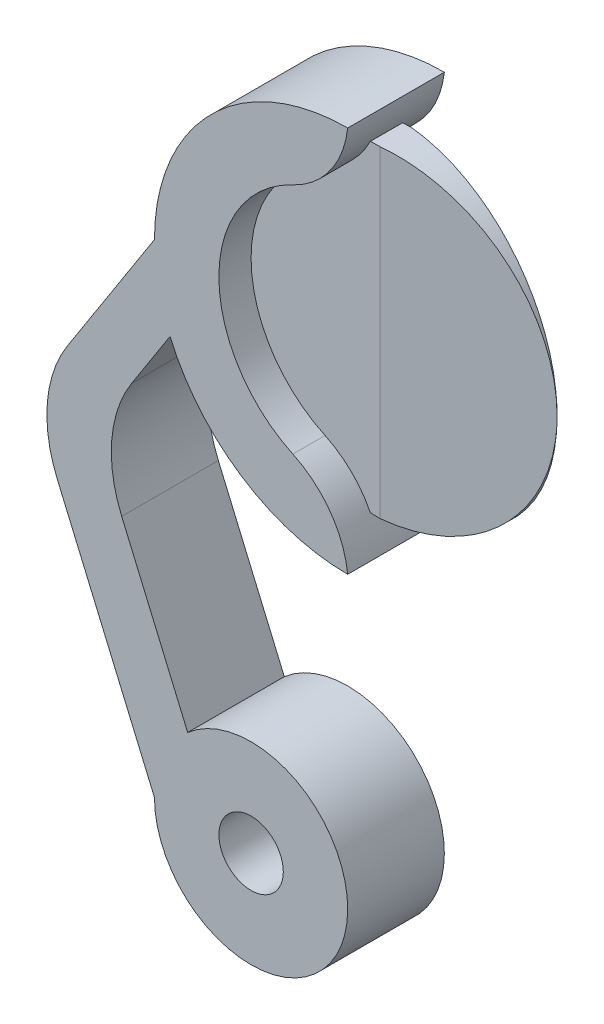
SolidWorks part; units mm, degrees
ref_plane "Front Plane" through (0, 0, 0) normal (0, 0, 1) x (1, 0, 0)
ref_plane "Top Plane" through (0, 0, 0) normal (0, 1, 0) x (1, 0, 0)
ref_plane "Right Plane" through (0, 0, 0) normal (1, 0, 0) x (0, 0, -1)
sketch "Sketch1" plane through (0, 0, 0) normal (0, 0, 1) x (1, 0, 0)
  line L0 (0, 0) -> (0, -120) construction
  line L1 (0, 0) -> (0, -10)
  line L2 (0, -50) -> (0, -60)
  line L4 (-30, -30) -> (-49.2547, -60)
  line L5 (-49.2547, -60) -> (-30, -105)
  line L6 (-20, -30) -> (-39.2547, -60)
  line L7 (-39.2547, -60) -> (-20, -105)
  line L8 (-30, -30) -> (-20, -30)
  line L9 (-30, -105) -> (-20, -105)
  arc A0 (0, -10) -> (0, -50) centre (0, -30) ccw
  arc A1 (0, 0) -> (0, -60) centre (0, -30) ccw
  circle A2 centre (-15, -105) radius 15
  circle A3 centre (-15, -105) radius 5
  dimension "D1" = 40
  dimension "D2" = 60
  dimension "D5" = 15
  dimension "D6" = 15
  dimension "D4" = 120
  dimension "D7" = 10
  dimension "D8" = 15
extrude "Boss-Extrude1" add sketch "Sketch1" along normal blind 15 contours L8 A1 L6 | L1 A1 L8 A0 | L6 A1 L2 A0 | A2 L7 L6 A1 L4 L5 | L7 A2 L9 | L7 A3 L9 A2 region at (-16.1277, -13.8723, 0) region at (-36.5183, -67.2913, 0) region at (-26.1035, -34.0913, 0) region at (-14.1866, -48.4697, 0) region at (-25.4415, -100.8757, 0) region at (-25, -105.4243, 0)
fillet "Fillet1" radius 20 2 edges at (-39.2547, -60, 7.5) (-49.2547, -60, 7.5)
fillet "Fillet2" radius 15 2 edges at (0, -50, 7.5) (0, -10, 7.5)
sketch "Sketch2" plane through (0, 0, 0) normal (1, 0, 0) x (0, 0, -1)
  line L0 (-15, 0) -> (0, 0) construction
  line L1 (-10, 0) -> (-5, 0)
  line L2 (-10, 0) -> (-10, -60)
  line L3 (-10, -60) -> (-5, -60)
  line L4 (-5, 0) -> (-5, -60)
  line L5 (-15, -60) -> (0, -60) construction
  line L6 (0, -48.0952) -> (0, -11.9048) construction
  dimension "D1" = 5
  dimension "D2" = 5
extrude "Boss-Extrude2" add sketch "Sketch2" along normal blind 25 and the other way blind 21
sketch "Sketch3" plane through (0, 0, 5) normal (0, 0, -1) x (-1, 0, 0)
  line L1 (-25, 0) -> (21, 0)
  line L2 (-25, 0) -> (-25, -60)
  line L3 (-25, -60) -> (21, -60)
  line L4 (21, 0) -> (21, -60)
  arc A0 (21, -16.4353) -> (21, -43.5647) centre (0, -30) ccw
  arc A1 (0, -60) -> (21, -51.4243) centre (0, -30) ccw
  arc A2 (21, -8.5757) -> (0, 0) centre (0, -30) ccw
  line M2 (-25, -60) -> (0, -60)
  arc M3 (0, -60) -> (8.5184, -48.0952) centre (14.9071, -61.6667) cw
  arc M5 (8.5184, -11.9048) -> (0, 0) centre (14.9071, 1.6667) cw
  line M6 (0, 0) -> (-25, 0)
  line M7 (-25, 0) -> (-25, -60)
extrude "Cut-Extrude1" cut sketch "Sketch3" against normal blind 5 contours A0 M5 M6 M7 | A2 L4 L1 | A0 L2 M2 M3 | A1 L3 L4 region at (15.8965, -6.6499, 5) region at (-15.9119, -2.4945, 5) region at (15.8965, -53.3501, 5) region at (-15.9119, -57.5055, 5)
sketch "Sketch4" plane through (0, 0, 0) normal (0, 1, 0) x (1, 0, 0)
  line L0 (25, -7.5) -> (0, -5)
  line L1 (25, -10) -> (25, -5) construction
  line L2 (0, -15) -> (0, 0) construction
  line L3 (25, -5) -> (-1.4922, -5) construction
  line L4 (0, -5) -> (25, -5)
  line L5 (25, -5) -> (25, -10)
  line L6 (25, -10) -> (0, -10)
  line L7 (-1.4922, -10) -> (25, -10) construction
  line L8 (0, -10) -> (25, -7.5)
extrude "Cut-Extrude2" cut sketch "Sketch4" against normal blind 62 contours L5 L4 L0 | L8 L6 L5 region at (16.6667, 0, 5.8333) region at (16.6667, 0, 9.1667)
